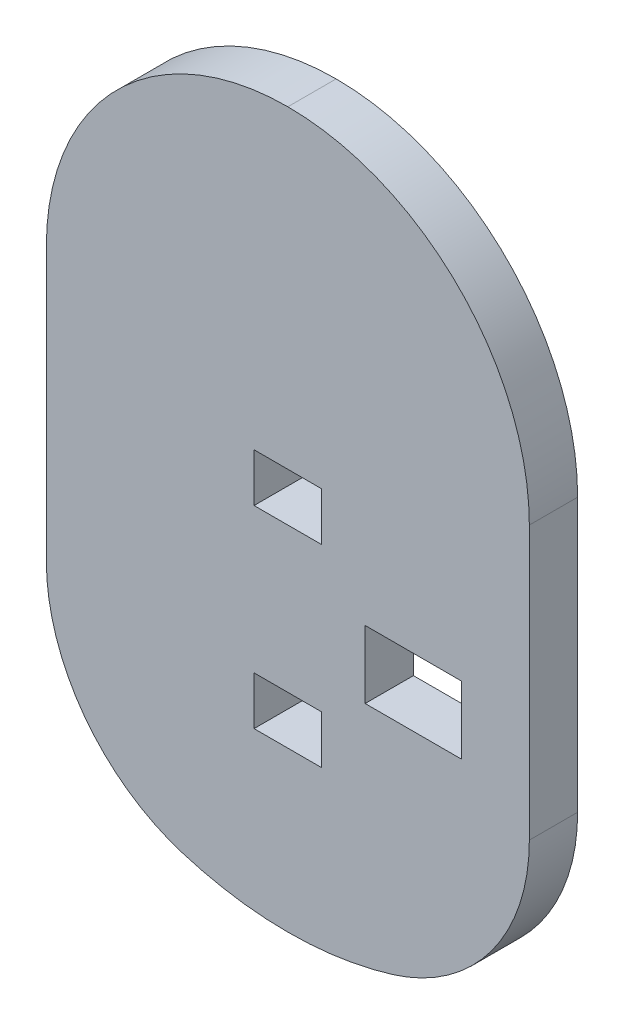
SolidWorks part; units mm, degrees
material "Acrylic (Medium-high impact)"
ref_plane "Front Plane" through (0, 0, 0) normal (0, 0, 1) x (1, 0, 0)
ref_plane "Top Plane" through (0, 0, 0) normal (0, 1, 0) x (1, 0, 0)
ref_plane "Right Plane" through (0, 0, 0) normal (1, 0, 0) x (0, 0, -1)
sketch "Sketch1" plane through (0, 0, 0) normal (0, 0, 1) x (1, 0, 0)
  circle A0 centre (0, 0) radius 37
  point P0 (0, 0)
  dimension "D1" = 74
extrude "Boss-Extrude1" add sketch "Sketch1" along normal blind 5
sketch "Sketch10" plane through (0, 0, 5) normal (0, 0, 1) x (1, 0, 0)
  line L0 (-25, 27.2764) -> (-25, -27.2764)
  line L2 (25, -27.2764) -> (25, 27.2764)
  circle A0 centre (0, 0) radius 37 construction
  arc A1 (-25, 27.2764) -> (-25, -27.2764) centre (0, 0) ccw
  circle A2 centre (0, 0) radius 37
  arc A3 (25, -27.2764) -> (25, 27.2764) centre (0, 0) ccw
  dimension "D2" = 25
  dimension "D3" = 50
  dimension "D1" = 0
extrude "Cut-Extrude3" cut sketch "Sketch10" against normal blind 10
fillet "Fillet1" radius 25 2 edges at (-25, 27.2764, 2.5) (25, 27.2764, 2.5)
fillet "Fillet2" radius 20 2 edges at (-25, -27.2764, 2.5) (25, -27.2764, 2.5)
sketch "Sketch11" plane through (0, 0, 5) normal (0, 0, 1) x (1, 0, 0)
  line L1 (-3.5, 4.5) -> (3.5, 4.5)
  line L2 (-3.5, 4.5) -> (-3.5, -0.5)
  line L3 (-3.5, -0.5) -> (3.5, -0.5)
  line L4 (3.5, 4.5) -> (3.5, -0.5)
  line L5 (-3.5, 4.5) -> (3.5, -0.5) construction
  line L6 (-3.5, -0.5) -> (3.5, 4.5) construction
  line L7 (-3.5, -15.5) -> (3.5, -15.5)
  line L8 (-3.5, -15.5) -> (-3.5, -20.5)
  line L9 (-3.5, -20.5) -> (3.5, -20.5)
  line L10 (3.5, -15.5) -> (3.5, -20.5)
  line L11 (-3.5, -15.5) -> (3.5, -20.5) construction
  line L12 (-3.5, -20.5) -> (3.5, -15.5) construction
  point P0 (0, 2)
  point P5 (0, -18)
  point P14 (0, -0.5)
  dimension "D1" = 32.5
  dimension "D2" = 25
  dimension "D3" = 7
  dimension "D4" = 5
extrude "Cut-Extrude4" cut sketch "Sketch11" against normal blind 10
sketch "Sketch4" plane through (0, 0, 5) normal (0, 0, 1) x (1, 0, 0)
  line L1 (-11, 4.5) -> (11, 4.5)
  line L2 (-11, 4.5) -> (-11, -0.5)
  line L3 (-11, -0.5) -> (11, -0.5)
  line L4 (11, 4.5) -> (11, -0.5)
  line L5 (-11, 4.5) -> (11, -0.5) construction
  line L6 (-11, -0.5) -> (11, 4.5) construction
  point P0 (0, 2)
  dimension "D1" = 22
  dimension "D2" = 5
  dimension "D3" = 2
extrude "Boss-Extrude2" [suppressed] add sketch "Sketch4" along normal blind 35
sketch "Sketch5" [suppressed] plane through (0, 4.5, 0) normal (0, 1, 0) x (1, 0, 0)
  line L1 (-6, -11) -> (6, -11)
  line L2 (-6, -11) -> (-6, -34)
  line L3 (-6, -34) -> (6, -34)
  line L4 (6, -11) -> (6, -34)
  line L5 (-6, -11) -> (6, -34) construction
  line L6 (-6, -34) -> (6, -11) construction
  line L7 (-11, -40) -> (-11, -5) construction
  line L8 (11, -40) -> (-11, -40) construction
  point P0 (0, -22.5)
  point P10 (-11, -22.5)
  point P12 (0, -40)
  dimension "D1" = 12
  dimension "D2" = 23
extrude "Cut-Extrude1" [suppressed] cut sketch "Sketch5" against normal blind 5
sketch "Sketch6" [suppressed] plane through (0, 4.5, 0) normal (0, 1, 0) x (1, 0, 0)
  line L0 (0, -8) -> (0, -37) construction
  line L1 (-6, -11) -> (-6, -34) construction
  line L2 (-6, -34) -> (6, -34) construction
  circle A0 centre (0, -8) radius 1.25
  circle A1 centre (0, -37) radius 1.25
  point P4 (0, -22.5)
  point P7 (-6, -22.5)
  point P10 (0, -34)
  dimension "D1" = 2.5
  dimension "D2" = 29
extrude "Cut-Extrude2" [suppressed] cut sketch "Sketch6" against normal blind 5
sketch "Sketch7" [suppressed] plane through (0, 0, 40) normal (0, 0, 1) x (1, 0, 0)
  line L0 (11, -0.5) -> (11, 4.5) construction
  line L1 (-11, 4.5) -> (11, 4.5)
  line L2 (-11, 4.5) -> (-11, -15.5)
  line L3 (-11, -15.5) -> (11, -15.5)
  line L4 (11, 4.5) -> (11, -15.5)
  line L5 (11, -0.5) -> (11, 4.5) construction
  dimension "D1" = 20
extrude "Boss-Extrude3" [suppressed] add sketch "Sketch7" along normal blind 5
sketch "Sketch8" [suppressed] plane through (0, -15.5, 0) normal (0, -1, 0) x (1, 0, 0)
  line L1 (-11, 45) -> (11, 45)
  line L2 (-11, 45) -> (-11, 5)
  line L3 (-11, 5) -> (11, 5)
  line L4 (11, 45) -> (11, 5)
extrude "Boss-Extrude4" [suppressed] add sketch "Sketch8" along normal blind 5
sketch "Sketch9" [suppressed] plane through (0, -20.5, 0) normal (0, -1, 0) x (1, 0, 0)
  line L0 (-11, 5) -> (11, 5) construction
  circle A0 centre (0, 27.5) radius 3.75
  dimension "D1" = 7.5
  dimension "D2" = 22.5
extrude "Boss-Extrude5" [suppressed] add sketch "Sketch9" along normal blind 7
fillet "Fillet3" [suppressed] radius 0.5
sketch "Sketch12" plane through (0, 0, 5) normal (0, 0, 1) x (1, 0, 0)
  line L6 (-3.5, -0.5) -> (3.5, -0.5) construction
  line L7 (8, -5.5) -> (18, -5.5)
  line L8 (8, -5.5) -> (8, -12.5)
  line L9 (8, -12.5) -> (18, -12.5)
  line L10 (18, -5.5) -> (18, -12.5)
  line L11 (25, 12) -> (25, -16.2481) construction
  dimension "D1" = 10
  dimension "D2" = 7
  dimension "D3" = 5
  dimension "D4" = 7
extrude "Cut-Extrude5" cut sketch "Sketch12" against normal blind 10
